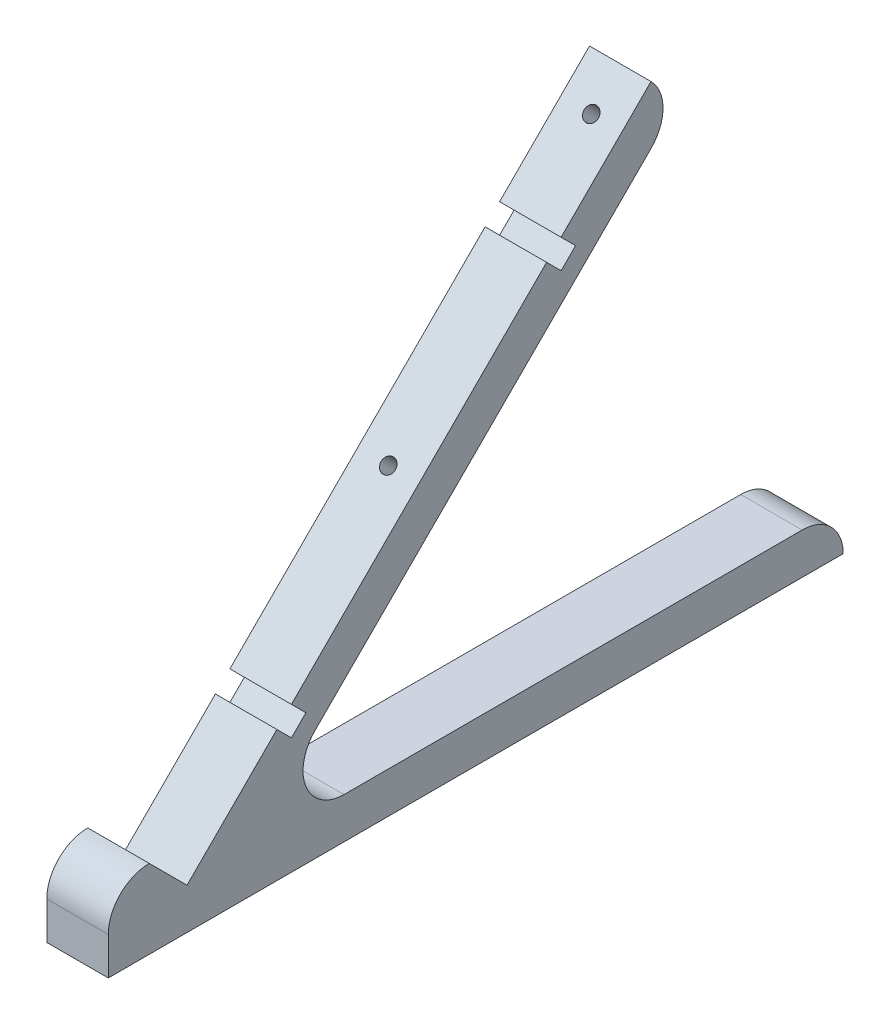
SolidWorks part; units mm, degrees
ref_plane "Front Plane" through (0, 0, 0) normal (0, 0, 1) x (1, 0, 0)
ref_plane "Top Plane" through (0, 0, 0) normal (0, 1, 0) x (1, 0, 0)
ref_plane "Right Plane" through (0, 0, 0) normal (1, 0, 0) x (0, 0, -1)
sketch "Sketch1" plane through (0, 0, 0) normal (1, 0, 0) x (0, 0, -1)
  line L0 (0, 10) -> (113.1371, 123.1371)
  line L1 (0, 0) -> (160, 0)
  line L2 (0, 0) -> (0, 10)
  line L3 (0, 10) -> (160, 10)
  line L4 (160, 0) -> (160, 10)
  line L5 (113.1371, 123.1371) -> (120.2082, 116.066)
  line L6 (120.2082, 116.066) -> (14.1421, 10)
  line L7 (0, 10) -> (0, 0)
  line L8 (0, 10) -> (-9.1924, 10)
  line L9 (0, 0) -> (-9.1924, 0)
  line L10 (-9.1924, 10) -> (-9.1924, 0)
  line L11 (0, 10) -> (-9.1924, 19.1924)
  line L12 (-9.1924, 19.1924) -> (-9.1924, 10)
  line L17 (-9.1924, 0) -> (-9.1924, 19.1924)
  line L18 (-9.1924, 0) -> (-19.1924, 0)
  line L19 (-9.1924, 19.1924) -> (-19.1924, 19.1924)
  line L20 (-19.1924, 0) -> (-19.1924, 19.1924)
  dimension "D1" = 160
  dimension "D2" = 10
  dimension "D3" = 360
  dimension "D4" = 10
  dimension "D5" = 45
  dimension "D6" = 160
  dimension "D7" = 90
  dimension "D8" = 13
  dimension "D9" = 45
  dimension "D10" = 10
extrude "Boss-Extrude1" add sketch "Sketch1" along normal blind 15 contours L6 L5 L0 L3 | L1 L4 L3 L2 | L8 L10 L9 L2 | L11 L12 L8 | L20 L18 L10 L12 L17 L19 | L17 L18 L20 L19 region at (0, 5, -80) region at (0, 64.8198, -61.8148) region at (0, 5, 4.5962) region at (0, 13.0641, 6.1283) region at (0, 9.5962, 14.1924)
sketch "Sketch2" plane through (0, 5, 5) normal (0, 0.7071, 0.7071) x (1, 0, 0)
  line L0 (7.5, 7.0711) -> (7.5, 167.0711) construction
  line L1 (0, 7.0711) -> (0, 167.0711) construction
  line L2 (15, 167.0711) -> (0, 167.0711) construction
  line L3 (15, 87.0711) -> (0, 87.0711) construction
  line L4 (15, 7.0711) -> (15, 167.0711) construction
  line L5 (0, 7.0711) -> (0, 167.0711) construction
  line L6 (15, 7.0711) -> (0, 7.0711) construction
  line L7 (0, 136.0711) -> (15, 136.0711)
  line L8 (0, 136.0711) -> (0, 131.0711)
  line L9 (0, 131.0711) -> (15, 131.0711)
  line L10 (15, 136.0711) -> (15, 131.0711)
  line L11 (15, 7.0711) -> (15, 167.0711) construction
  line L12 (0, 43.0711) -> (15, 43.0711)
  line L13 (15, 38.0711) -> (15, 43.0711)
  line L14 (0, 38.0711) -> (0, 43.0711)
  line L15 (0, 38.0711) -> (15, 38.0711)
  circle A0 centre (7.5, 87.0711) radius 1.75
  circle A1 centre (7.5, 157.0711) radius 1.75
  circle A3 centre (7.5, 87.0711) radius 3.25
  circle A4 centre (7.5, 157.0711) radius 3.25
  line M4 (0, 167.0711) -> (0, 7.0711)
  line M6 (15, 7.0711) -> (15, 167.0711)
  dimension "D1" = 3.5
  dimension "D3" = 70
  dimension "D6" = 6.5
  dimension "D4" = 31
  dimension "D5" = 5
  dimension "D2" = 2
extrude "Cut-Extrude1" cut sketch "Sketch2" against normal up to next contours A4 A1 | A1 | A3 A0 | A0 region at (7.5, 66.5685, -56.5685) region at (7.5, 116.066, -106.066) region at (4.3419, 66.5685, -56.5685) region at (4.3419, 116.066, -106.066)
fillet "Fillet1" radius 10 4 edges at (7.5, 10, -14.1421) (7.5, 116.066, -120.2082) (7.5, 10, -160) (7.5, 19.1924, 19.1924)
extrude "Cut-Extrude2" cut sketch "Sketch2<3>" against normal blind 5 contours L9 L7 M4 M6 | L15 L12 M4 M6 region at (7.5, 99.449, -89.449) region at (7.5, 33.6881, -23.6881)
sketch "Sketch2<3>" plane through (0, 5, 5) normal (0, 0.7071, 0.7071) x (1, 0, 0) same geometry as "Sketch2"
extrude "Boss-Extrude2" add sketch "Sketch2<4>" against normal blind 5 contours A3 A0 | A4 A1 region at (4.3419, 66.5685, -56.5685) region at (4.3419, 116.066, -106.066)
sketch "Sketch2<4>" plane through (0, 5, 5) normal (0, 0.7071, 0.7071) x (1, 0, 0) same geometry as "Sketch2"
